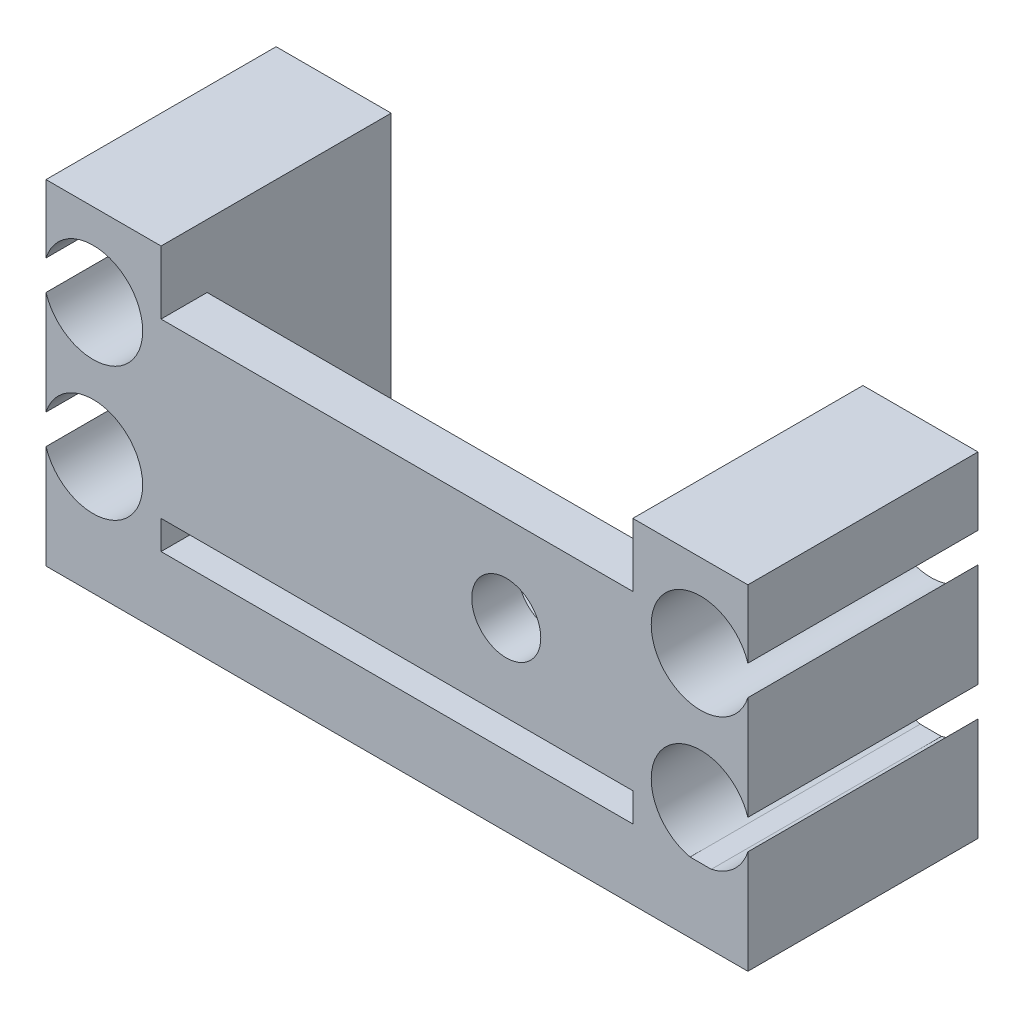
SolidWorks part; units mm, degrees
ref_plane "Спереди" through (0, 0, 0) normal (0, 0, 1) x (1, 0, 0)
ref_plane "Сверху" through (0, 0, 0) normal (0, 1, 0) x (1, 0, 0)
ref_plane "Справа" through (0, 0, 0) normal (1, 0, 0) x (0, 0, -1)
sketch "Эскиз1" plane through (0, 0, 0) normal (0, 0, 1) x (1, 0, 0)
  line L2 (-61.1906, -40.1769) -> (-61.1906, -15.0857)
  line L3 (-61.1906, -15.0857) -> (-51.1906, -15.0857)
  line L4 (-0.1906, -38.0857) -> (-0.1906, -15.0857)
  line L8 (-0.1906, -15.0857) -> (-10.1906, -15.0857)
  line L9 (-10.1906, -15.0857) -> (-10.1906, -38.0857)
  line L10 (-51.1906, -15.0857) -> (-51.1906, -38.0857)
  line L11 (-51.1906, -38.0857) -> (-10.1906, -38.0857)
  line L12 (-61.1906, -40.1769) -> (-61.1906, -44.1769)
  line L13 (-61.1906, -44.1769) -> (-0.1906, -44.1769)
  line L14 (-0.1906, -44.1769) -> (-0.1906, -38.0857)
  point P0 (0, 0)
extrude "Бобышка-Вытянуть1" add sketch "Эскиз1" along normal blind 20
sketch "Эскиз3" plane through (-61.1906, 0, 0) normal (-1, 0, 0) x (0, 0, 1)
  line L5 (0, -15.0857) -> (0, -44.1769) construction
  line L6 (15, -15.0857) -> (0, -15.0857) construction
  line L7 (15, -15.0857) -> (15, -38.2478) construction
  line L8 (15, -38.2478) -> (0, -38.2478) construction
  line L9 (0, -15.0857) -> (0, -38.2478) construction
  point P7 (0, 0)
sketch "Эскиз5" plane through (0, 0, 20) normal (0, 0, 1) x (1, 0, 0)
  line L0 (-51.1906, -38.0857) -> (-51.1906, -15.0857) construction
  line L1 (-10.1906, -28.0857) -> (-24.1906, -28.0857) construction
  line L12 (-10.1906, -38.0857) -> (-51.1906, -38.0857) construction
  line L13 (-10.1906, -38.0857) -> (-10.1906, -18.0857) construction
  line L14 (-10.1906, -18.0857) -> (-51.1906, -18.0857) construction
  line L15 (-51.1906, -38.0857) -> (-51.1906, -18.0857) construction
  line L16 (-21.1906, -35.5857) -> (-51.1906, -35.5857)
  line L18 (-21.1906, -20.5857) -> (-51.1906, -20.5857)
  line L19 (-51.1906, -35.5857) -> (-51.1906, -20.5857)
  line L20 (-21.1906, -20.5857) -> (-10.1906, -20.5857)
  line L22 (-21.1906, -35.5857) -> (-10.1906, -35.5857)
  line L23 (-10.1906, -20.5857) -> (-10.1906, -35.5857)
  circle A5 centre (-21.1906, -28.0857) radius 3
  point P10 (0, 0)
  point P11 (0, 0)
extrude "Бобышка-Вытянуть6" add sketch "Эскиз5" against normal blind 4
sketch "Эскиз6" plane through (0, 0, 20) normal (0, 0, 1) x (1, 0, 0)
  line L0 (-51.1906, -20.5857) -> (-51.1906, -15.0857) construction
  line L1 (-10.1906, -38.0857) -> (-51.1906, -38.0857)
  line L2 (-10.1906, -38.0857) -> (-10.1906, -18.0857)
  line L3 (-10.1906, -18.0857) -> (-51.1906, -18.0857)
  line L4 (-51.1906, -38.0857) -> (-51.1906, -18.0857)
  line L5 (-10.1906, -38.0857) -> (-0.1906, -38.0857)
  line L6 (-0.1906, -44.1769) -> (-0.1906, -15.0857) construction
  line L7 (-4.2906, -38.0857) -> (-4.2906, -29.5857) construction
  line L8 (-10.1906, -35.5857) -> (-4.2906, -35.5857) construction
  line L9 (-10.1906, -18.0857) -> (-0.1906, -18.0857) construction
  line L10 (-4.2906, -18.0857) -> (-4.2906, -26.5857) construction
  line L11 (-4.2906, -22.2857) -> (-10.1906, -22.2857) construction
  line L12 (-30.6906, -38.0857) -> (-30.6906, -18.0857) construction
  circle A1 centre (-4.2906, -33.8857) radius 4.3
  circle A3 centre (-4.2906, -22.2857) radius 4.3
  circle A4 centre (-57.0906, -22.2857) radius 4.3
  circle A5 centre (-57.0906, -33.8857) radius 4.3
  line M16 (-61.1906, -15.0857) -> (-61.1906, -44.1769)
  line M18 (-0.1906, -44.1769) -> (-0.1906, -15.0857)
extrude "Вырез-Вытянуть1" cut sketch "Эскиз6" against normal through all contours A1 L5 M18 | A3 M18 | A5 M16 | A4 M16 region at (-4.3157, -22.2857, 20) region at (-4.3158, -33.8767, 20) region at (-57.0654, -22.2857, 20) region at (-57.0654, -33.8857, 20)
